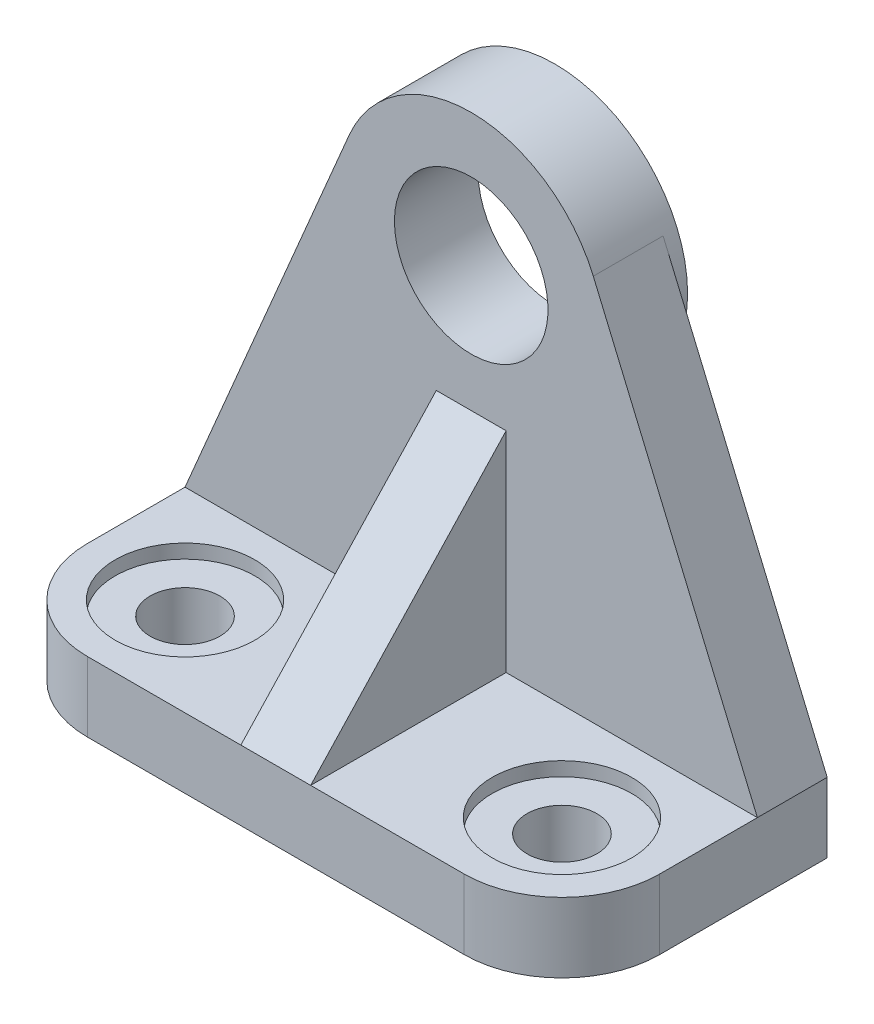
SolidWorks part; units mm, degrees
ref_plane "Front Plane" through (0, 0, 0) normal (0, 0, 1) x (1, 0, 0)
ref_plane "Top Plane" through (0, 0, 0) normal (0, 1, 0) x (1, 0, 0)
ref_plane "Right Plane" through (0, 0, 0) normal (1, 0, 0) x (0, 0, -1)
sketch "Sketch1" plane through (0, 0, 0) normal (0, 1, 0) x (1, 0, 0)
  line L1 (-41, 19) -> (41, 19)
  line L2 (-41, 19) -> (-41, -19)
  line L3 (-41, -19) -> (41, -19)
  line L4 (41, 19) -> (41, -19)
  line L5 (-41, 19) -> (41, -19) construction
  line L6 (-41, -19) -> (41, 19) construction
  point P0 (0, 0)
  dimension "D1" = 82
  dimension "D2" = 38
extrude "Boss-Extrude1" add sketch "Sketch1" along normal blind 10
sketch "Sketch4" plane through (0, 0, -19) normal (0, 0, -1) x (-1, 0, 0)
  line L0 (0, 0) -> (0, 58) construction
  line L1 (-41, 0) -> (41, 0) construction
  line L2 (-41, 10) -> (-17.4914, 65.4197)
  line L3 (41, 10) -> (17.4914, 65.4197)
  line L4 (-41, 10) -> (41, 10)
  circle A0 centre (0, 58) radius 19
  line M5 (41, 10) -> (-41, 10)
  dimension "D1" = 38
  dimension "D2" = 58
extrude "Boss-Extrude3" add sketch "Sketch4" against normal blind 10 contours L4 L0 A0 L2 | L0 L3 A0 M5 region at (17.85, 27.0662, -19) region at (-17.85, 27.0662, -19)
extrude "Boss-Extrude4" add sketch "Sketch4<3>" along normal blind 12 from offset 10 contours A0 region at (0, 58, -19) offset against normal yes
sketch "Sketch4<3>" plane through (0, 0, -19) normal (0, 0, -1) x (-1, 0, 0) same geometry as "Sketch4"
sketch "Sketch5" plane through (0, 0, -21) normal (0, 0, -1) x (-1, 0, 0)
  circle A0 centre (0, 58) radius 11
  dimension "D1" = 22
extrude "Cut-Extrude2" cut sketch "Sketch5" against normal through all
fillet "Fillet1" radius 14 2 edges at (41, 5, 19) (-41, 5, 19)
sketch "Sketch6" plane through (0, 10, 0) normal (0, 1, 0) x (1, 0, 0)
  line L0 (0, 25.3653) -> (0, -37.0407) construction
  circle A0 centre (-27, -5) radius 10
  dimension "D1" = 20
extrude "Cut-Extrude3" cut sketch "Sketch6" against normal blind 2 contours A0
sketch "Sketch7" plane through (0, 8, 0) normal (0, 1, 0) x (1, 0, 0)
  circle A0 centre (-27, -5) radius 5
  dimension "D1" = 10
extrude "Cut-Extrude4" cut sketch "Sketch7" against normal through all contours A0
sketch "Sketch8" plane through (0, 0, 0) normal (1, 0, 0) x (0, 0, -1)
  line L0 (-19, 10) -> (9, 40)
  line L1 (9, 10) -> (9, 65.4197) construction
  dimension "D1" = 30
rib "Rib1" sketch "Sketch8" sketch "Sketch8" thickness 10 extrusion direction parallel to sketch draft on no parameters "D1"=10
mirror "Mirror1" about plane through (0, 0, 0) normal (1, 0, 0) of "Cut-Extrude3"
mirror "Mirror2" about plane through (0, 0, 0) normal (1, 0, 0) of "Cut-Extrude4"
